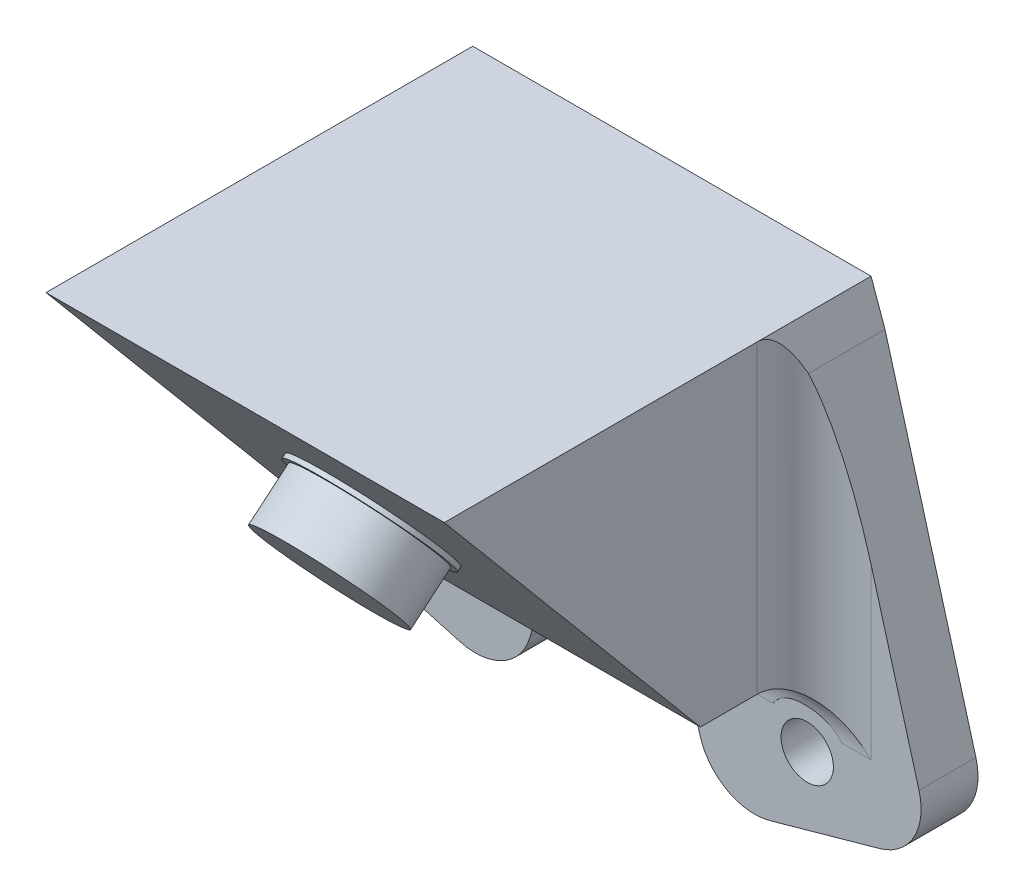
SolidWorks part; units mm, degrees
ref_plane "Ebene vorne" through (0, 0, 0) normal (0, 0, 1) x (1, 0, 0)
ref_plane "Ebene oben" through (0, 0, 0) normal (0, 1, 0) x (1, 0, 0)
ref_plane "Ebene rechts" through (0, 0, 0) normal (1, 0, 0) x (0, 0, -1)
sketch "Skizze1" plane through (0, 0, 0) normal (1, 0, 0) x (0, 0, -1)
  line L0 (0, 0) -> (26.8116, 0)
  line L1 (0, 0) -> (0, 15)
  line L2 (0, 15) -> (26.8116, 37.4976)
  line L3 (26.8116, 37.4976) -> (26.8116, 0)
  dimension "D1" = 40
  dimension "D2" = 15
  dimension "D3" = 35
extrude "Aufsatz-Linear austragen1" add sketch "Skizze1" along normal blind 35
sketch "Skizze3" plane through (0, 8.8024, 7.3861) normal (0, 0.766, 0.6428) x (1, 0, 0)
  line L0 (0, 44.6418) -> (35, 9.6418) construction
  line L1 (17.5, 27.1418) -> (35, 44.6418) construction
  circle A0 centre (17.5, 27.1418) radius 6
  dimension "D1" = 12
extrude "Aufsatz-Linear austragen2" add sketch "Skizze3" along normal blind 5
sketch "Skizze4" plane through (0, 8.8024, 7.3861) normal (0, 0.766, 0.6428) x (1, 0, 0)
  circle A0 centre (17.5, 27.1418) radius 6.5
  dimension "D1" = 13
extrude "Aufsatz-Linear austragen3" add sketch "Skizze4" along normal blind 0.4
ref_plane "Ebene1" through (0, 15, 0) normal (0, -1, 0) x (-1, 0, 0)
sketch "Skizze7" plane through (0, 15, 0) normal (0, -1, 0) x (-1, 0, 0)
  line L1 (-35, 0) -> (0, 26.8116) construction
  line L2 (-17.5, 13.4058) -> (-17.5, 26.8116) construction
  line L3 (-35, 26.8116) -> (0, 26.8116) construction
  line L4 (-17.5, 13.4058) -> (-35, 13.4058) construction
  line L5 (-35, 0) -> (-35, 26.8116) construction
  circle A0 centre (-28.5, 21.8116) radius 2.85
  circle A1 centre (-6.5, 21.8116) radius 2.85
  circle A2 centre (-6.5, 5) radius 2.85
  circle A3 centre (-28.5, 5) radius 2.85
  dimension "D1" = 5.7
  dimension "D2" = 11
  dimension "D3" = 5
extrude "Schnitt-Linear austragen1" [suppressed] cut sketch "Skizze7" against normal through all
hole_wizard "Ø3.4 (3.4) Durchmesser Bohrung1" [suppressed] positions "3D-Skizze3" profile "Skizze8" hole size "Ø3.4" standard "DIN"
sketch3d "3D-Skizze3" [suppressed]
  line L0 (6.5, 35.6935, -21.8116) -> (6.5, 15, -21.8116) construction
  line L1 (6.5, 21.5869, -5) -> (6.5, 15, -5) construction
  line L2 (28.5, 21.5869, -5) -> (28.5, 15, -5) construction
  line L3 (28.5, 35.6935, -21.8116) -> (28.5, 15, -21.8116) construction
  point P0 (6.5, 15, -21.8116)
  point P4 (6.5, 15, -5)
  point P8 (28.5, 15, -5)
  point P12 (28.5, 15, -21.8116)
sketch "Skizze8" plane through (6.5, 15, -21.8116) normal (1, 0, 0) x (0, 0, 1)
  line L0 (0, 0) -> (0, 15)
  line L1 (0, 15) -> (1.7, 15)
  line L2 (1.7, 15) -> (1.7, 0)
  line L5 (1.7, 0) -> (0, 0)
  line L11 (0, -6.35) -> (0, 107.95) construction
  dimension "Bohrerdurchmesser" = 3.4
  dimension "Bohrungstiefe" = 15
move or copy body "Körper-Verschieben/Kopieren1" bodies to move or copy 103 copy no rotation origin (0, 13.6438, -13.4058) rotation axis (1, 0, 0) rotation angle 90
sketch "Skizze9" plane through (0, 0, -27.0496) normal (0, 0, -1) x (-1, 0, 0)
  line L0 (-13.0068, 0.238) -> (-8.7008, -15.1717)
  line L1 (-35, 0.238) -> (0, 0.238) construction
  line L2 (63.2379, -272.6139) -> (-17.5, 16.3175) construction
  line L3 (-8.7008, -15.1717) -> (10.5613, -9.7891)
  line L4 (82.5, -267.2314) -> (1.7621, 21.7) construction
  line L5 (10.5613, -9.7891) -> (1.2238, 23.6263)
  line L6 (1.2238, 23.6263) -> (0, 27.0496)
  line L7 (0, 27.0496) -> (0, 0.238)
  line L8 (0, 0.238) -> (-13.0068, 0.238)
  line L9 (-17.5, 0.238) -> (-17.5, 7.6415) construction
  line L10 (-45.5613, -9.7891) -> (-36.2238, 23.6263)
  line L11 (-26.2992, -15.1717) -> (-45.5613, -9.7891)
  line L12 (-21.9932, 0.238) -> (-26.2992, -15.1717)
  line L13 (-35, 0.238) -> (-21.9932, 0.238)
  line L14 (-35, 27.0496) -> (-35, 0.238)
  line L15 (-36.2238, 23.6263) -> (-35, 27.0496)
  line L16 (0.9303, -12.4804) -> (-2.4788, -0.2805) construction
  circle A0 centre (-0.6094, -6.9704) radius 2.3
  circle A1 centre (-34.3906, -6.9704) radius 2.3
  dimension "D2" = 4.6
  dimension "D1" = 16
extrude "Aufsatz-Linear austragen4" add sketch "Skizze9" against normal blind 5
fillet "Verrundung1" radius 5 10 edges at (35, 13.6438, -22.0496) (28.4966, 0.238, -22.0496) (6.5034, 0.238, -22.0496) (0, 13.6438, -22.0496) (45.5613, -9.7891, -24.5496) (26.2992, -15.1717, -24.5496) (8.7008, -15.1717, -24.5496) (-10.5613, -9.7891, -24.5496) (21.9932, 0.238, -24.5496) (13.0068, 0.238, -24.5496)
sketch "Skizze11" plane through (0, 0, -22.0496) normal (0, 0, 1) x (1, 0, 0)
  circle A0 centre (0.6094, -6.9704) radius 3.75
  circle A1 centre (34.3906, -6.9704) radius 3.75
  dimension "D1" = 7.5
extrude "Schnitt-Linear austragen2" cut sketch "Skizze11" along normal blind 10
sketch "Skizze12" plane through (0, 0, -27.0496) normal (0, 0, -1) x (-1, 0, 0)
  circle A0 centre (-17.5, 21.8738) radius 1.425
  dimension "D1" = 2.85
extrude "Schnitt-Linear austragen3" cut sketch "Skizze12" against normal blind 9
